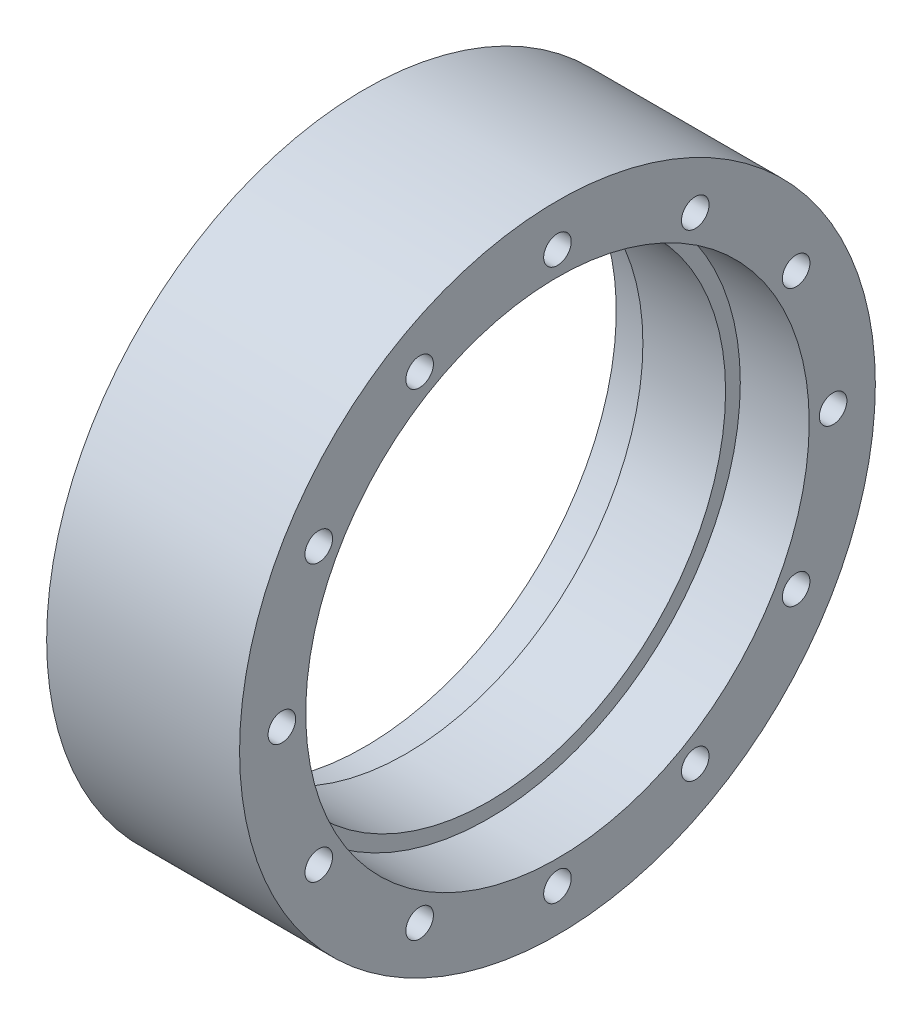
SolidWorks part; units mm, degrees
ref_plane "Front Plane" through (0, 0, 0) normal (0, 0, 1) x (1, 0, 0)
ref_plane "Top Plane" through (0, 0, 0) normal (0, 1, 0) x (1, 0, 0)
ref_plane "Right Plane" through (0, 0, 0) normal (1, 0, 0) x (0, 0, -1)
sketch "Sketch2" plane through (0, 0, 0) normal (1, 0, 0) x (0, 0, -1)
  circle A0 centre (0, 0) radius 29
  circle A1 centre (0, 0) radius 36.62
  dimension "D1" = 58
  dimension "D2" = 7.62
extrude "Boss-Extrude1" add sketch "Sketch2" along normal mid plane 25.4
sketch "Sketch4" plane through (-12.7, 0, 0) normal (-1, 0, 0) x (0, 0, 1)
  circle A0 centre (0, 0) radius 27.305
  circle A1 centre (0, 0) radius 36.62
  dimension "D1" = 54.61
extrude "Boss-Extrude2" add sketch "Sketch4" along normal mid plane 9.525 from surface starting at plane "Right Plane"
sketch "Sketch5" plane through (12.7, 0, 0) normal (1, 0, 0) x (0, 0, -1)
  line L0 (0, 0) -> (31.75, 0) construction
  circle A0 centre (31.75, 0) radius 1.5875
  circle A1 centre (27.4963, -15.875) radius 1.5875
  circle A2 centre (15.875, -27.4963) radius 1.5875
  circle A3 centre (0, -31.75) radius 1.5875
  circle A4 centre (-15.875, -27.4963) radius 1.5875
  circle A5 centre (-27.4963, -15.875) radius 1.5875
  circle A6 centre (-31.75, 0) radius 1.5875
  circle A7 centre (-27.4963, 15.875) radius 1.5875
  circle A8 centre (-15.875, 27.4963) radius 1.5875
  circle A9 centre (0, 31.75) radius 1.5875
  circle A10 centre (15.875, 27.4963) radius 1.5875
  circle A11 centre (27.4963, 15.875) radius 1.5875
  point P29 (0, 0)
  dimension "D2" = 3.175
  dimension "D1" = 31.75
  dimension "D3" = 12
extrude "Cut-Extrude2" cut sketch "Sketch5" against normal through all
ref_axis "Axis1" through (13.97, 0, 0) along (-1, 0, 0)
sketch "Sketch6" plane through (-12.7, 0, 0) normal (-1, 0, 0) x (0, 0, 1)
  circle A0 centre (0, 0) radius 63.5
  dimension "D1" = 127
extrude "Cut-Extrude3" cut sketch "Sketch6" against normal blind 3.175
